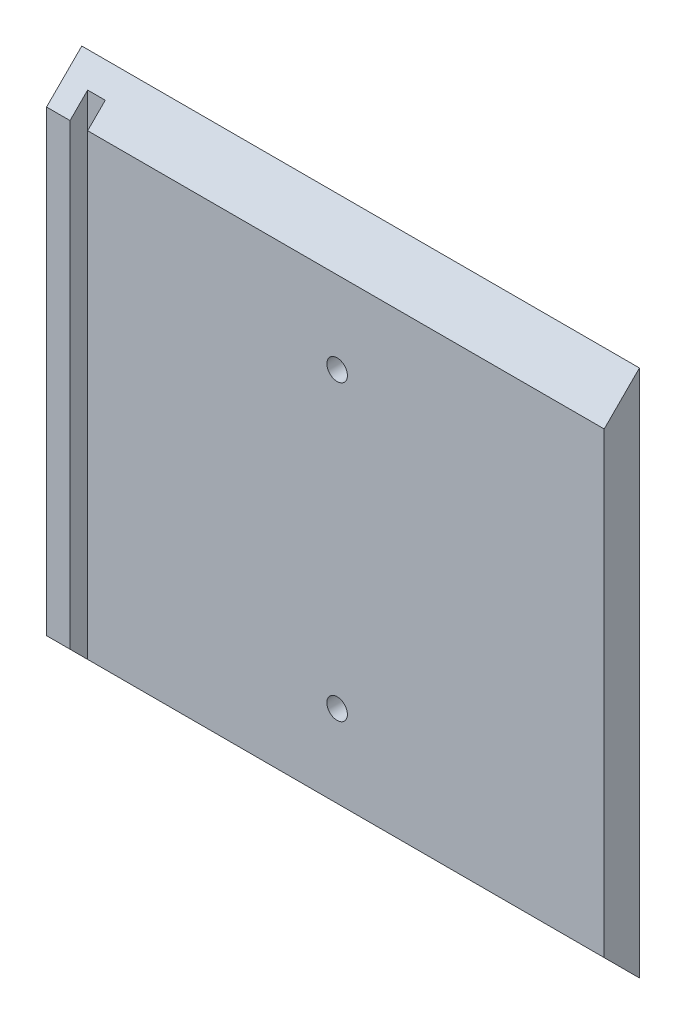
SolidWorks part; units mm, degrees
material "Maple"
ref_plane "Front Plane" through (0, 0, 0) normal (0, 0, 1) x (1, 0, 0)
ref_plane "Top Plane" through (0, 0, 0) normal (0, 1, 0) x (1, 0, 0)
ref_plane "Right Plane" through (0, 0, 0) normal (1, 0, 0) x (0, 0, -1)
sketch "Sketch1" plane through (0, 0, 0) normal (0, 0, 1) x (1, 0, 0)
  line L1 (-47.5, -45) -> (47.5, -45)
  line L2 (-47.5, -45) -> (-47.5, 45)
  line L3 (-47.5, 45) -> (47.5, 45)
  line L4 (47.5, -45) -> (47.5, 45)
  line L5 (-47.5, -45) -> (47.5, 45) construction
  line L6 (-47.5, 45) -> (47.5, -45) construction
  point P0 (0, 0)
  dimension "D1" = 95
  dimension "D2" = 90
extrude "Boss-Extrude1" add sketch "Sketch1" along normal blind 6
chamfer "Chamfer1" distance 6 angle 45 2 edges at (0, -45, 6) (0, 45, 6)
sketch "Sketch2" plane through (0, 0, 6) normal (0, 0, 1) x (1, 0, 0)
  line L0 (47.5, 45) -> (-47.5, 45) construction
  line L1 (-43.5, -45) -> (-40.5, -45)
  line L2 (-43.5, -45) -> (-43.5, 45)
  line L3 (-43.5, 45) -> (-40.5, 45)
  line L4 (-40.5, -45) -> (-40.5, 45)
  line L5 (-43.5, -45) -> (-40.5, 45) construction
  line L6 (-43.5, 45) -> (-40.5, -45) construction
  line L7 (-47.5, -45) -> (47.5, -45) construction
  line L8 (-47.5, 39) -> (-47.5, -39) construction
  point P0 (-42, 0)
  dimension "D1" = 3
  dimension "D2" = 4
extrude "Cut-Extrude1" cut sketch "Sketch2" against normal blind 3
sketch "Sketch3" [suppressed] plane through (0, 0, 0) normal (0, 0, -1) x (-1, 0, 0)
  line L1 (-45, -45) -> (-45, 45) construction
  circle A0 centre (-7, 20) radius 5
  dimension "D3" = 6
  dimension "D1" = 32
  dimension "D2" = 20
extrude "Cut-Extrude2" [suppressed] cut sketch "Sketch3" against normal through all
mirror "Mirror1" [suppressed] about plane through (0, 0, 0) normal (0, 1, 0)
sketch "Sketch4" plane through (0, 0, 0) normal (0, 0, -1) x (-1, 0, 0)
  line L0 (-2, 25) -> (-2, -25) construction
  line L1 (-47.5, 0) -> (47.5, 0) construction
  line L2 (-47.5, -45) -> (-47.5, 45) construction
  line L3 (47.5, 45) -> (47.5, -45) construction
  circle A0 centre (-2, 25) radius 1.75
  circle A1 centre (-2, -25) radius 1.75
  point P10 (-2, 0)
  dimension "D1" = 3.5
  dimension "D2" = 50
  dimension "D3" = 49.5
extrude "Cut-Extrude3" cut sketch "Sketch4" against normal through all
